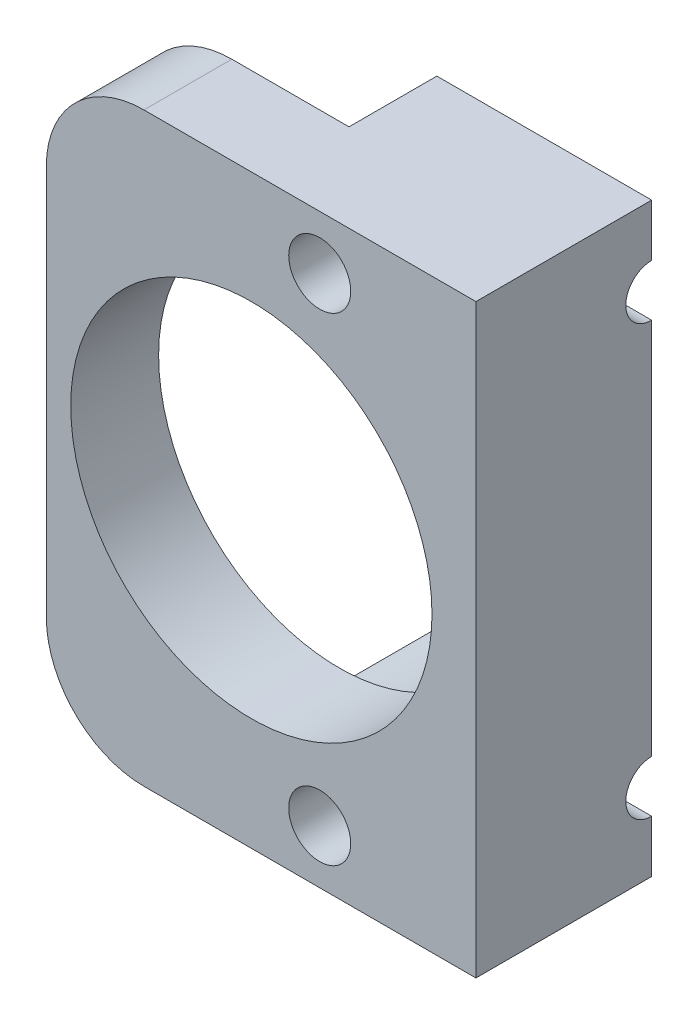
SolidWorks part; units mm, degrees
material "6061-T6 (SS)"
ref_plane "Front Plane" through (0, 0, 0) normal (0, 0, 1) x (1, 0, 0)
ref_plane "Top Plane" through (0, 0, 0) normal (0, 1, 0) x (1, 0, 0)
ref_plane "Right Plane" through (0, 0, 0) normal (1, 0, 0) x (0, 0, -1)
sketch "Sketch1" plane through (0, 0, 0) normal (0, 0, 1) x (1, 0, 0)
  line L0 (-21, 30) -> (-21, -30)
  line L1 (-21, -30) -> (23, -30)
  line L2 (0, 0) -> (18.5, 0) construction
  line L4 (23, 30) -> (23, -30)
  line L5 (-21, 30) -> (23, 30)
  circle A0 centre (0, 0) radius 18.5
  arc A1 (0, 21) -> (-21, 0) centre (0, 0) ccw construction
  arc A2 (-21, 0) -> (0, 21) centre (0, 0) ccw construction
  point P10 (23, 0)
  dimension "D1" = 37
  dimension "D2" = 42
  dimension "D3" = 30
  dimension "D4" = 23
extrude "Boss-Extrude1" add sketch "Sketch1" along normal mid plane 9
sketch "Sketch3" plane through (0, 0, -4.5) normal (0, 0, -1) x (-1, 0, 0)
  line L0 (-23, 30) -> (-1, 30)
  line L1 (-23, 30) -> (21, 30) construction
  line L2 (-1, 30) -> (-1, 18.9737)
  line L3 (-23, 30) -> (-23, -30)
  line L4 (-23, -30) -> (-23, 30) construction
  line L5 (0, 0) -> (-18.5, 0) construction
  line L6 (-23, -30) -> (-1, -30)
  line L7 (-1, -30) -> (-1, -18.9737)
  circle A0 centre (0, 0) radius 18.5 construction
  arc A2 (-1, -18.9737) -> (-1, 18.9737) centre (0, 0) ccw construction
  arc A3 (-1, 18.9737) -> (-1, -18.9737) centre (0, 0) ccw
  dimension "D2" = 19
  dimension "D1" = 1
extrude "Boss-Extrude2" add sketch "Sketch3" along normal blind 9
fillet "Fillet1" radius 10 2 edges at (-21, -30, 0) (-21, 30, 0)
sketch "Sketch5" plane through (0, 0, -13.5) normal (0, 0, -1) x (-1, 0, 0)
  line L1 (-1, 30) -> (-23, 30) construction
  line L3 (0, 0) -> (-18.5, 0) construction
  line L4 (-23, 30) -> (-23, -30) construction
  circle A0 centre (-7, 24.5) radius 3.175
  circle A1 centre (0, 0) radius 18.5 construction
  circle A2 centre (-7, -24.5) radius 3.175
  dimension "D1" = 6.35
  dimension "D2" = 16
  dimension "D3" = 5.5
extrude "Cut-Extrude1" cut sketch "Sketch5" against normal through all
sketch "Sketch6" plane through (0, 0, -13.5) normal (0, 0, -1) x (-1, 0, 0)
  line L0 (-1, 30) -> (-23, 30) construction
  line L1 (-14.5, 22) -> (-14.5, 26) construction
  line L2 (-14.5, 22) -> (-12, 22) construction
  line L3 (-15.5, 18) -> (-13.5, 18)
  line L4 (-17, 19.5) -> (-17, 24.5)
  line L5 (-15.5, 26) -> (-13.5, 26)
  line L6 (-12, 19.5) -> (-12, 24.5)
  line L7 (-17, 18) -> (-12, 26) construction
  line L8 (-17, 26) -> (-12, 18) construction
  line L9 (-23, 30) -> (-23, -30) construction
  line L10 (0, 0) -> (-18.5, 0) construction
  line L15 (-17, 24.5) -> (-17, 26) construction
  line L16 (-17, 26) -> (-15.5, 26) construction
  line L17 (-13.5, 26) -> (-12, 26) construction
  line L18 (-12, 24.5) -> (-12, 26) construction
  line L19 (-12, 18) -> (-12, 19.5) construction
  line L20 (-13.5, 18) -> (-12, 18) construction
  line L21 (-17, 18) -> (-15.5, 18) construction
  line L22 (-17, 18) -> (-17, 19.5) construction
  line L23 (-15.5, -18) -> (-13.5, -18)
  line L24 (-12, -19.5) -> (-12, -24.5)
  line L25 (-15.5, -26) -> (-13.5, -26)
  line L26 (-17, -19.5) -> (-17, -24.5)
  circle A2 centre (0, 0) radius 18.5 construction
  arc A4 (-17, 24.5) -> (-15.5, 26) centre (-16.25, 25.25) cw
  arc A5 (-12, 24.5) -> (-13.5, 26) centre (-12.75, 25.25) ccw
  arc A6 (-12, 19.5) -> (-13.5, 18) centre (-12.75, 18.75) cw
  arc A7 (-17, 19.5) -> (-15.5, 18) centre (-16.25, 18.75) ccw
  arc A8 (-17, -19.5) -> (-15.5, -18) centre (-16.25, -18.75) cw
  arc A9 (-12, -19.5) -> (-13.5, -18) centre (-12.75, -18.75) ccw
  arc A10 (-12, -24.5) -> (-13.5, -26) centre (-12.75, -25.25) cw
  arc A11 (-17, -24.5) -> (-15.5, -26) centre (-16.25, -25.25) ccw
  point P0 (-14.5, 22)
  dimension "D3" = 4
  dimension "D5" = 1.5
  dimension "D1" = 8
  dimension "D2" = 5
  dimension "D4" = 6
  dimension "D6" = 1.5
extrude "Cut-Extrude2" cut sketch "Sketch6" against normal blind 4.75
fillet "Fillet2" radius 1 16 edges at (17, -19.5, -11.125) (17, -24.5, -11.125) (15.5, -26, -11.125) (13.5, -26, -11.125) (12, -24.5, -11.125) (12, -19.5, -11.125) (13.5, -18, -11.125) (15.5, -18, -11.125) (17, 24.5, -11.125) (17, 19.5, -11.125) (15.5, 18, -11.125) (13.5, 18, -11.125) (12, 19.5, -11.125) (12, 24.5, -11.125) (13.5, 26, -11.125) (15.5, 26, -11.125)
sketch "Sketch8" plane through (17, 0, 0) normal (-1, 0, 0) x (0, 0, 1)
  line L0 (-13.5, -19.838) -> (-13.5, -24.162) construction
  line L1 (-13.5, 24.162) -> (-13.5, 19.838) construction
  point P0 (-13.5, 22)
  point P1 (-13.5, -22)
hole_wizard "M5 Clearance Hole1" positions "Sketch9" profile "Sketch10" hole size "M5" standard "ANSI Metric" end condition through all
sketch "Sketch9" plane through (17, 0, 0) normal (-1, 0, 0) x (0, 0, 1)
  point P0 (-13.5, -22)
  point P3 (-13.5, 22)
sketch "Sketch10" plane through (17, -22, -13.5) normal (0, 1, 0) x (0, 0, 1)
  line L0 (0, 0) -> (0, 6)
  line L1 (0, 6) -> (2.65, 6)
  line L2 (2.65, 6) -> (2.65, 0)
  line L5 (2.65, 0) -> (0, 0)
  line L11 (0, -6.35) -> (0, 107.95) construction
  dimension "Thru Hole Dia." = 5.3
  dimension "Thru Hole Depth" = 6
equation "\"D1@Sketch5\"=0.25in"
